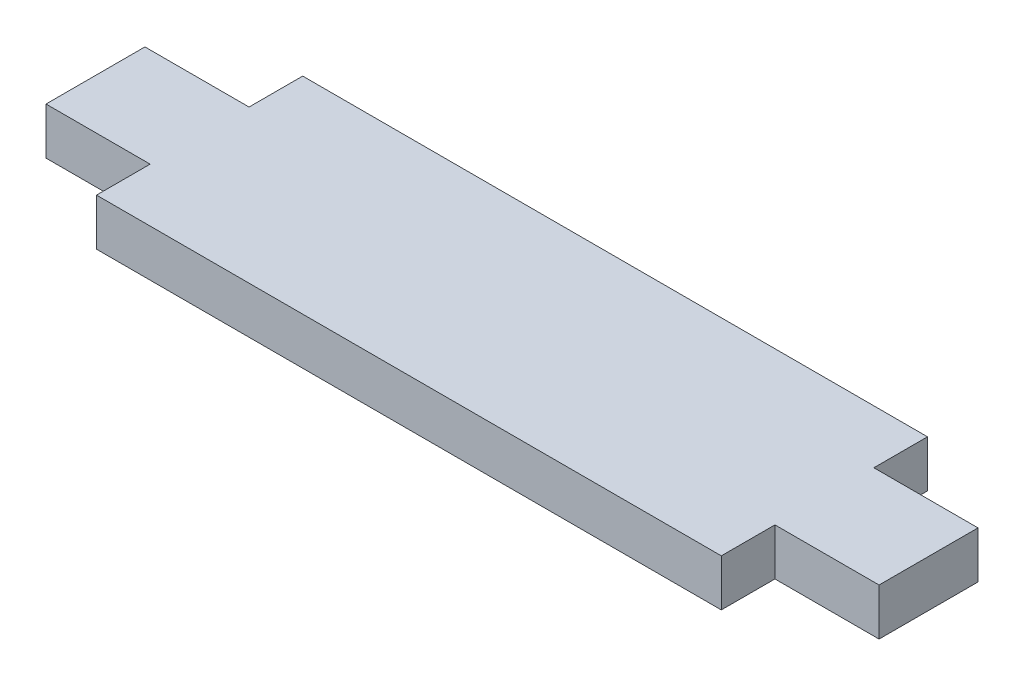
SolidWorks part; units mm, degrees
ref_plane "Front Plane" through (0, 0, 0) normal (0, 0, 1) x (1, 0, 0)
ref_plane "Top Plane" through (0, 0, 0) normal (0, 1, 0) x (1, 0, 0)
ref_plane "Right Plane" through (0, 0, 0) normal (1, 0, 0) x (0, 0, -1)
sketch "Sketch1" plane through (0, 0, 0) normal (1, 0, 0) x (0, 0, -1)
  line L1 (-9.9, -2.25) -> (9.9, -2.25)
  line L2 (-9.9, -2.25) -> (-9.9, 2.25)
  line L3 (-9.9, 2.25) -> (9.9, 2.25)
  line L4 (9.9, -2.25) -> (9.9, 2.25)
  line L5 (-9.9, -2.25) -> (9.9, 2.25) construction
  line L6 (-9.9, 2.25) -> (9.9, -2.25) construction
  point P0 (0, 0)
  dimension "D1" = 4.5
  dimension "D2" = 19.8
extrude "Boss-Extrude1" add sketch "Sketch1" along normal mid plane 60
sketch "Sketch2" plane through (30, 0, 0) normal (1, 0, 0) x (0, 0, -1)
  line L1 (-4.75, -2.25) -> (4.75, -2.25)
  line L2 (-4.75, -2.25) -> (-4.75, 2.25)
  line L3 (-4.75, 2.25) -> (4.75, 2.25)
  line L4 (4.75, -2.25) -> (4.75, 2.25)
  point P0 (-4.75, 0)
  point P6 (0, 2.25)
  dimension "D1" = 9.5
  dimension "D2" = 4.5
extrude "Boss-Extrude2" add sketch "Sketch2" along normal blind 10
mirror "Mirror1" about plane through (0, 0, 0) normal (1, 0, 0) of "Boss-Extrude2"
